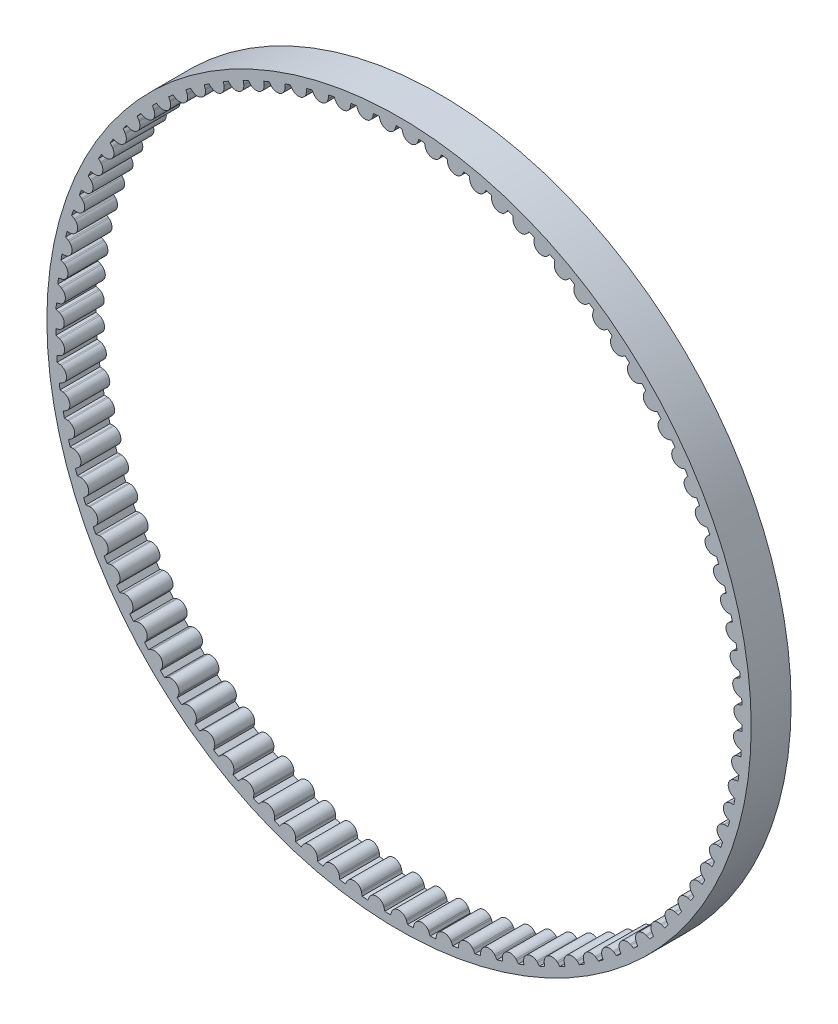
SolidWorks part; units mm, degrees
ref_plane "Face" through (0, 0, 0) normal (0, 0, 1) x (1, 0, 0)
ref_plane "Dessus" through (0, 0, 0) normal (0, 1, 0) x (1, 0, 0)
ref_plane "Droite" through (0, 0, 0) normal (1, 0, 0) x (0, 0, -1)
sketch "Esquisse1" plane through (0, 0, 0) normal (0, 0, 1) x (1, 0, 0)
  line L0 (0, 0) -> (-0.9998, 30.2229) construction
  line L1 (0, 0) -> (0.9998, 30.2229) construction
  line L2 (-1.0206, 30.8499) -> (-0.9998, 30.2229)
  line L3 (1.0206, 30.8499) -> (0.9998, 30.2229)
  line L4 (-1.3995, 30.207) -> (0, 0) construction
  line L5 (0, 0) -> (0, 30.8668) construction
  line L6 (-0.9703, 29.3307) -> (0, 0) construction
  line L7 (0, 0) -> (0.9703, 29.3307) construction
  line L8 (-0.9703, 29.3307) -> (-0.9914, 29.969)
  line L9 (0.9703, 29.3307) -> (0.9914, 29.969)
  line L10 (0.9914, 29.969) -> (0.9998, 30.2229)
  line L11 (-0.9914, 29.969) -> (-0.9998, 30.2229)
  line L12 (-1.0132, 30.6287) -> (-0.9998, 30.2229)
  line L13 (1.0132, 30.6287) -> (0.9998, 30.2229)
  line L14 (-0.3212, 29.8371) -> (-0.2534, 30.0798)
  line L15 (-0.2534, 30.0798) -> (0.2534, 30.0798)
  line L16 (0.3212, 29.8371) -> (0.2534, 30.0798)
  arc A0 (-0.9998, 30.2229) -> (0.9998, 30.2229) centre (0, 0) cw construction
  arc A1 (1.0206, 30.8499) -> (-1.0206, 30.8499) centre (0, 0) ccw
  arc A2 (0.9914, 29.969) -> (-0.9914, 29.969) centre (0, 0) ccw construction
  arc A3 (-0.9998, 30.2229) -> (-1.3995, 30.207) centre (0, 0) ccw construction
  arc A4 (-0.9914, 29.969) -> (-1.3877, 29.9533) centre (0, 0) ccw construction
  arc A5 (-0.9749, 29.4706) -> (-0.4867, 29.7987) centre (-0.9933, 30.0253) ccw construction
  arc A6 (-0.4867, 29.7987) -> (-0.4536, 29.8825) centre (-1.3995, 30.207) ccw construction
  arc A7 (0.9933, 30.0253) -> (-0.9933, 30.0253) centre (0, 0) ccw construction
  arc A8 (-0.4536, 29.8825) -> (-0.3133, 29.9838) centre (-0.3117, 29.8338) cw construction
  arc A9 (-0.3133, 29.9838) -> (0.3133, 29.9838) centre (0, 0) cw construction
  arc A10 (0.4536, 29.8825) -> (0.3133, 29.9838) centre (0.3117, 29.8338) ccw construction
  arc A11 (0.4867, 29.7987) -> (0.4536, 29.8825) centre (1.3995, 30.207) cw construction
  arc A12 (0.9749, 29.4706) -> (0.4867, 29.7987) centre (0.9933, 30.0253) cw construction
  arc A13 (-0.9703, 29.3307) -> (-0.3589, 29.7416) centre (-0.9933, 30.0253) ccw
  arc A14 (-0.3589, 29.7416) -> (-0.3212, 29.8371) centre (-1.3995, 30.207) ccw
  arc A15 (-0.3212, 29.8371) -> (-0.3119, 29.8438) centre (-0.3117, 29.8338) cw construction
  arc A16 (-0.3119, 29.8438) -> (0.3119, 29.8438) centre (0, 0) cw construction
  arc A17 (0.3212, 29.8371) -> (0.3119, 29.8438) centre (0.3117, 29.8338) ccw construction
  arc A18 (0.3589, 29.7416) -> (0.3212, 29.8371) centre (1.3995, 30.207) cw
  arc A19 (0.9703, 29.3307) -> (0.3589, 29.7416) centre (0.9933, 30.0253) cw
  arc A20 (1.0132, 30.6287) -> (-1.0132, 30.6287) centre (0, 0) ccw construction
  point P45 (0, 30.0798)
  dimension "D3" = 0.555
  dimension "D8" = 1
  dimension "D7" = 0.15
  dimension "D1" = 3.789
  dimension "D2" = 0.254
  dimension "D6" = 1.38
  dimension "D10" = 0.8
  dimension "D4" = 2
  dimension "D5" = 0.4
  dimension "D9" = 0.14
extrude "Boss-Extrude2" add sketch "Esquisse1" along normal blind 3.5 contours A19 L9 L10 L3 A1 L2 L11 L8 A13 A14 L14 L15 L16 A18 region at (0, 30.229, 0)
pattern_circular "CirPattern1" count 95 over 360 about axis through (0, 0, 3.5) along (0, 0, 1) of "Boss-Extrude2"
equation "\"n\"= 95"
equation "\"D1@CirPattern1\"=\"n\""
equation "\"D1@Esquisse1\"=360/\"n\""
